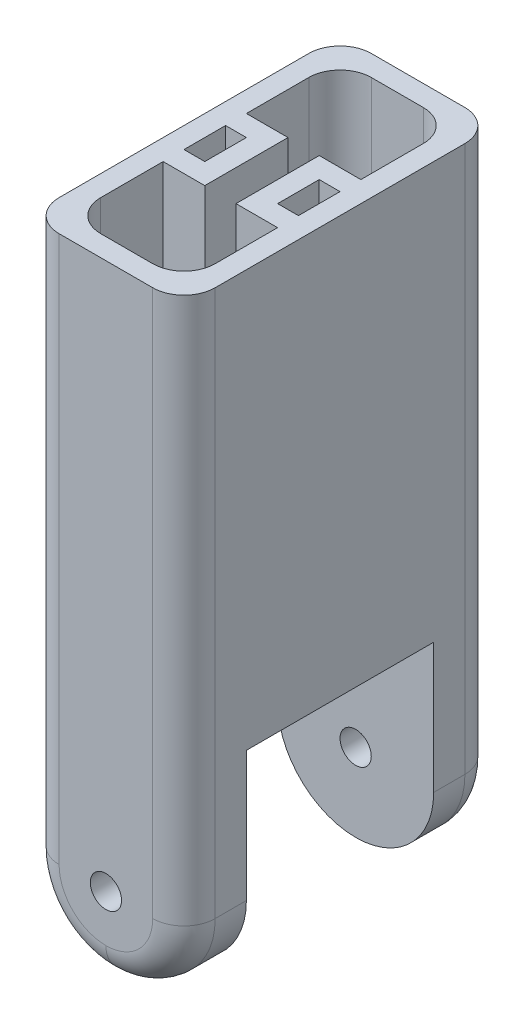
SolidWorks part; units mm, degrees
ref_plane "Front Plane" through (0, 0, 0) normal (0, 0, 1) x (1, 0, 0)
ref_plane "Top Plane" through (0, 0, 0) normal (0, 1, 0) x (1, 0, 0)
ref_plane "Right Plane" through (0, 0, 0) normal (1, 0, 0) x (0, 0, -1)
sketch "Sketch1" plane through (0, 0, 0) normal (0, 1, 0) x (1, 0, 0)
  line L0 (0, 0) -> (-10.7454, 0) construction
  line L1 (-7.5, -15) -> (7.5, -15)
  line L2 (-7.5, -15) -> (-7.5, 15)
  line L3 (-7.5, 15) -> (7.5, 15)
  line L4 (7.5, -15) -> (7.5, 15)
  line L5 (-7.5, -15) -> (7.5, 15) construction
  line L6 (-7.5, 15) -> (7.5, -15) construction
  line L7 (-5.5, -13) -> (5.5, -13)
  line L8 (-5.5, -13) -> (-5.5, -4)
  line L9 (-5.5, 13) -> (5.5, 13)
  line L10 (5.5, -13) -> (5.5, -4)
  line L11 (-5.5, -13) -> (5.5, 13) construction
  line L12 (-5.5, 13) -> (5.5, -13) construction
  line L13 (-10.7454, 0) -> (11.7241, 0) construction
  line L14 (-5.5, 4) -> (-1.5, 4)
  line L15 (-1.5, 4) -> (-1.5, -4)
  line L16 (-1.5, -4) -> (-5.5, -4)
  line L17 (-5.5, 2) -> (-3.5, 2)
  line L18 (-3.5, 2) -> (-3.5, -2)
  line L19 (-3.5, -2) -> (-5.5, -2)
  line L20 (5.5, 4) -> (1.5, 4)
  line L21 (1.5, 4) -> (1.5, -4)
  line L22 (1.5, -4) -> (5.5, -4)
  line L23 (5.5, 2) -> (3.5, 2)
  line L24 (3.5, 2) -> (3.5, -2)
  line L25 (3.5, -2) -> (5.5, -2)
  line L26 (-5.5, 4) -> (-5.5, 13)
  line L27 (5.5, 4) -> (5.5, 13)
  line L28 (-5.5, 2) -> (-5.5, -2)
  line L29 (5.5, 2) -> (5.5, -2)
  point P0 (0, 0)
  point P6 (0, 0)
  dimension "D1" = 2
  dimension "D2" = 2
  dimension "D3" = 2
  dimension "D4" = 2
  dimension "D5" = 2
  dimension "D6" = 2
  dimension "D7" = 2
  dimension "D8" = 2
  dimension "D9" = 2
  dimension "D10" = 2
  dimension "D11" = 30
  dimension "D12" = 15
  dimension "D13" = 8
  dimension "D14" = 8
  dimension "D15" = 2
extrude "Boss-Extrude1" add sketch "Sketch1" along normal blind 40
sketch "Sketch2" plane through (0, 0, 0) normal (0, -1, 0) x (1, 0, 0)
  line L0 (-7.5, -15) -> (-7.5, 15) construction
  line L1 (7.5, 15) -> (-7.5, 15)
  line L2 (7.5, 15) -> (7.5, 9)
  line L3 (7.5, 9) -> (-7.5, 9)
  line L4 (-7.5, 15) -> (-7.5, 9)
  line L6 (7.5, -15) -> (-7.5, -15)
  line L7 (7.5, -15) -> (7.5, -9)
  line L8 (7.5, -9) -> (-7.5, -9)
  line L9 (-7.5, -15) -> (-7.5, -9)
  dimension "D1" = 6
  dimension "D2" = 6
extrude "Boss-Extrude2" add sketch "Sketch2" along normal blind 20
fillet "Fillet1" radius 7.5 4 edges at (-7.5, -20, 12) (-7.5, -20, -12) (7.5, -20, -12) (7.5, -20, 12)
sketch "Sketch3" plane through (0, 0, 15) normal (0, 0, 1) x (1, 0, 0)
  circle A0 centre (0, -12.5) radius 1.5
  dimension "D1" = 3
extrude "Cut-Extrude1" cut sketch "Sketch3" against normal through all
fillet "Fillet2" radius 3 12 edges at (5.3033, -17.8033, 15) (-5.3033, -17.8033, 15) (-5.3033, -17.8033, -15) (7.5, 13.75, 15) (5.5, 20, -13) (-7.5, 13.75, 15) (-7.5, 13.75, -15) (5.3033, -17.8033, -15) (5.5, 20, 13) (-5.5, 20, 13) (7.5, 13.75, -15) (-5.5, 20, -13)
